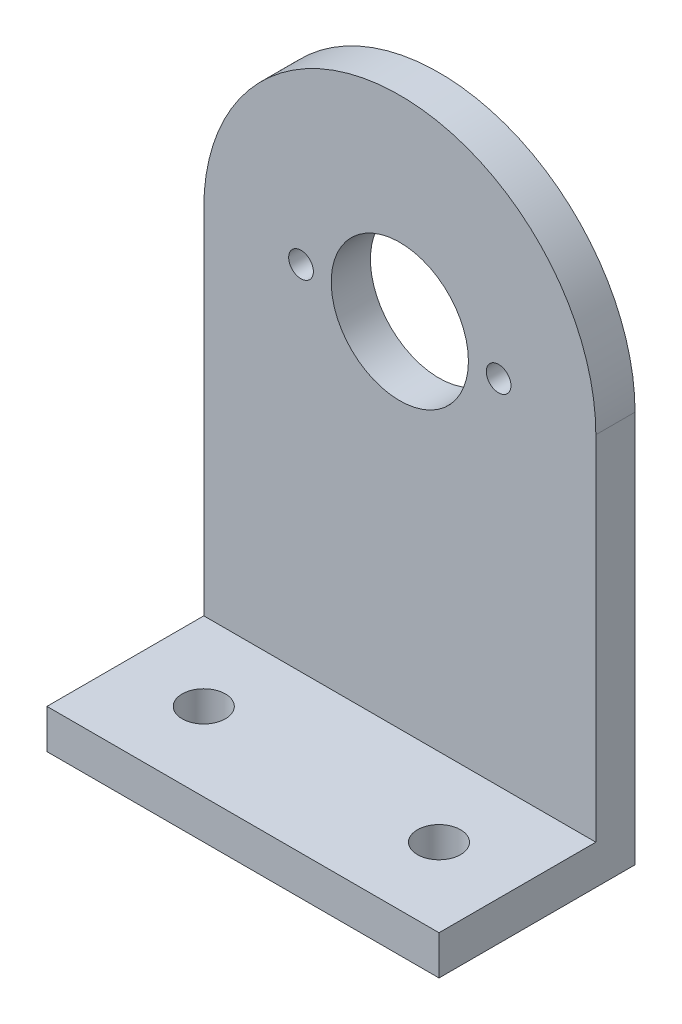
SolidWorks part; units mm, degrees
ref_plane "Front Plane" through (0, 0, 0) normal (0, 0, 1) x (1, 0, 0)
ref_plane "Top Plane" through (0, 0, 0) normal (0, 1, 0) x (1, 0, 0)
ref_plane "Right Plane" through (0, 0, 0) normal (1, 0, 0) x (0, 0, -1)
sketch "Sketch1" plane through (0, 0, 0) normal (0, 0, 1) x (1, 0, 0)
  line L1 (-15.875, 0) -> (15.875, 0)
  line L2 (-15.875, 0) -> (-15.875, -31.75)
  line L3 (-15.875, -31.75) -> (15.875, -31.75)
  line L4 (15.875, 0) -> (15.875, -31.75)
  circle A0 centre (0, 0) radius 15.875
  arc A2 (-15.875, 0) -> (15.875, 0) centre (0, 0) ccw
  dimension "D1" = 31.75
  dimension "D2" = 31.75
extrude "Boss-Extrude1" add sketch "Sketch1" along normal blind 3.175 contours A0 | L2 L1 L4 L3
sketch "Sketch3" plane through (0, 0, 3.175) normal (0, 0, 1) x (1, 0, 0)
  circle A0 centre (0, 0) radius 5.5562
  dimension "D1" = 11.1125
extrude "Cut-Extrude1" cut sketch "Sketch3" against normal through all
sketch "Sketch4" plane through (0, 0, 3.175) normal (0, 0, 1) x (1, 0, 0)
  line L0 (15.875, 0) -> (15.875, -31.75) construction
  line L1 (-15.875, -31.75) -> (15.875, -31.75)
  line L2 (-15.875, -31.75) -> (-15.875, -28.575)
  line L3 (-15.875, -28.575) -> (15.875, -28.575)
  line L4 (15.875, -31.75) -> (15.875, -28.575)
  dimension "D1" = 3.175
extrude "Boss-Extrude2" add sketch "Sketch4" along normal blind 12.7
sketch "Sketch5" plane through (0, -28.575, 0) normal (0, 1, 0) x (1, 0, 0)
  line L0 (-15.875, -9.525) -> (15.875, -9.525) construction
  line L1 (-15.875, -15.875) -> (-15.875, -3.175) construction
  line L2 (15.875, -15.875) -> (15.875, -3.175) construction
  line L3 (0, -3.175) -> (0, -15.875) construction
  line L4 (15.875, -3.175) -> (-15.875, -3.175) construction
  line L5 (15.875, -15.875) -> (-15.875, -15.875) construction
  circle A0 centre (-9.525, -9.525) radius 1.75
  circle A1 centre (9.525, -9.525) radius 1.75
  dimension "D1" = 3.5
  dimension "D2" = 9.525
extrude "Cut-Extrude2" cut sketch "Sketch5" against normal through all
hole_wizard "Ø2.0mm Dowel Hole1" positions "Sketch8" profile "Sketch9" hole size "Ø2.0" standard "ANSI Metric"
sketch "Sketch8" plane through (0, 0, 3.175) normal (0, 0, 1) x (1, 0, 0)
  line L0 (-15.875, 0) -> (15.875, 0) construction
  point P0 (-8.001, 0)
  point P2 (8.001, 0)
  dimension "D1" = 16.002
  dimension "D2" = 8.001
sketch "Sketch9" plane through (-8.001, 0, 3.175) normal (1, 0, 0) x (0, -1, 0)
  line L0 (0, 0) -> (0, 13.3009)
  line L1 (0, 13.3009) -> (1, 12.7)
  line L2 (1, 12.7) -> (1, 0)
  line L5 (1, 0) -> (0, 0)
  line L10 (0, 13.3009) -> (-1, 12.7) construction
  line L11 (0, -6.35) -> (0, 107.95) construction
  dimension "Hole Dia." = 2
  dimension "Hole Depth" = 12.7
  dimension "Drill Angle" = 118
chamfer "Chamfer1" distance 0.762 angle 45 2 edges at (-7.001, 0, 0) (9.001, 0, 0)
